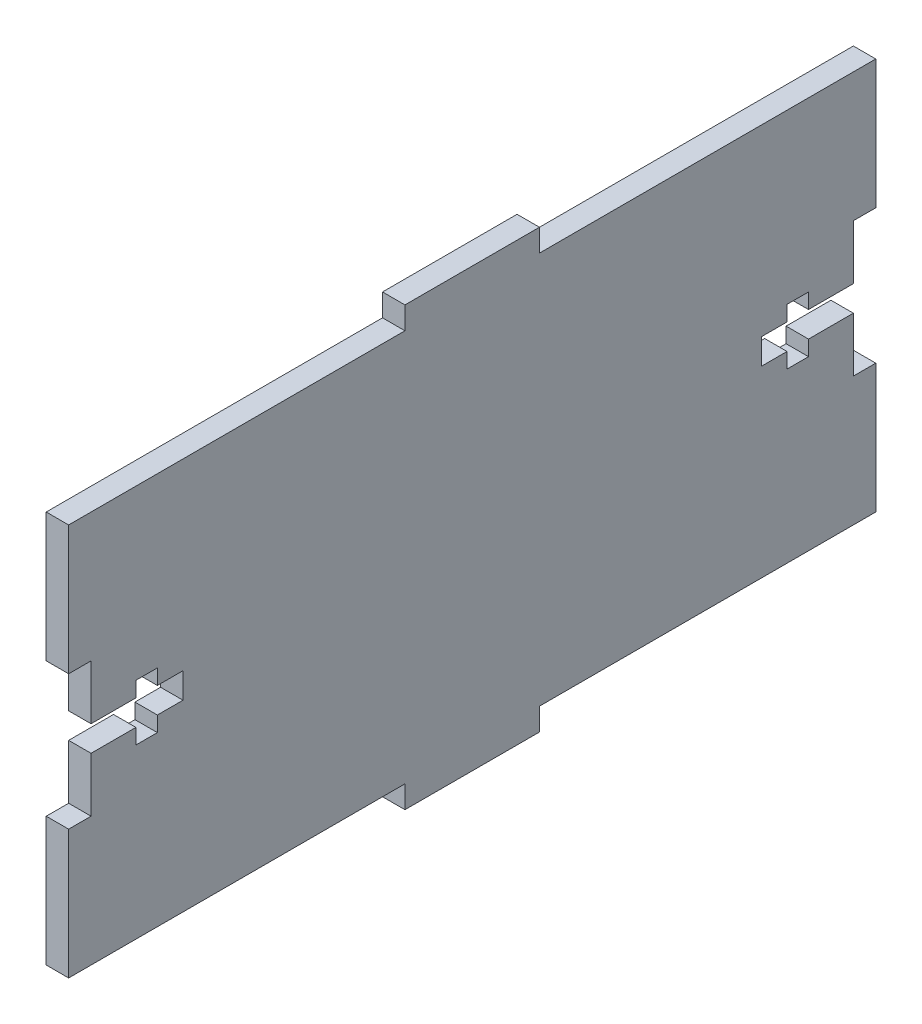
SolidWorks part; units mm, degrees
ref_plane "Front Plane" through (0, 0, 0) normal (0, 0, 1) x (1, 0, 0)
ref_plane "Top Plane" through (0, 0, 0) normal (0, 1, 0) x (1, 0, 0)
ref_plane "Right Plane" through (0, 0, 0) normal (1, 0, 0) x (0, 0, -1)
sketch "Sketch2" plane through (0, 0, 0) normal (1, 0, 0) x (0, 0, -1)
  line L0 (-45.72, 22.225) -> (-45.72, 7.62)
  line L1 (-45.72, 22.225) -> (45.72, 22.225) construction
  line L2 (-45.72, 22.225) -> (-45.72, -22.225) construction
  line L3 (-45.72, -22.225) -> (45.72, -22.225) construction
  line L4 (45.72, 22.225) -> (45.72, -22.225) construction
  line L5 (-45.72, 22.225) -> (45.72, -22.225) construction
  line L6 (-45.72, -22.225) -> (45.72, 22.225) construction
  line L7 (-45.72, 7.62) -> (-43.18, 7.62)
  line L8 (-43.18, 7.62) -> (-43.18, -7.62) construction
  line L9 (-43.18, -7.62) -> (-45.72, -7.62)
  line L10 (-45.72, -7.62) -> (-45.72, -22.225)
  line L11 (0, 22.225) -> (0, -22.225) construction
  line L12 (-45.72, 0) -> (45.72, 0) construction
  line L13 (43.18, -7.62) -> (45.72, -7.62)
  line L14 (43.18, 7.62) -> (43.18, -7.62) construction
  line L15 (45.72, 7.62) -> (43.18, 7.62)
  line L16 (-45.72, -22.225) -> (-7.62, -22.225)
  line L17 (-7.62, -22.225) -> (-7.62, -24.765)
  line L18 (-7.62, -24.765) -> (7.62, -24.765)
  line L19 (7.62, -24.765) -> (7.62, -22.225)
  line L20 (7.62, -22.225) -> (45.72, -22.225)
  line L21 (45.72, -22.225) -> (45.72, -7.62)
  line L22 (45.72, 7.62) -> (45.72, 22.225)
  line L23 (7.62, 24.765) -> (7.62, 22.225)
  line L24 (-7.62, 24.765) -> (7.62, 24.765)
  line L25 (-7.62, 22.225) -> (-7.62, 24.765)
  line L26 (45.72, 22.225) -> (7.62, 22.225)
  line L27 (-7.62, 22.225) -> (-45.72, 22.225)
  line L28 (-43.18, 7.62) -> (-43.18, 1.4478)
  line L29 (-43.18, 1.4478) -> (-38.1, 1.4478)
  line L30 (-38.1, 1.4478) -> (-38.1, 3.175)
  line L31 (-38.1, 3.175) -> (-35.6679, 3.175)
  line L32 (-35.6679, 3.175) -> (-35.6679, 1.4478)
  line L33 (-35.6679, 1.4478) -> (-32.766, 1.4478)
  line L34 (-32.766, 1.4478) -> (-32.766, -1.4478)
  line L35 (-38.1, -3.175) -> (-35.6679, -3.175)
  line L36 (-35.6679, -1.4478) -> (-32.766, -1.4478)
  line L37 (-35.6679, -3.175) -> (-35.6679, -1.4478)
  line L38 (-38.1, -1.4478) -> (-38.1, -3.175)
  line L39 (-43.18, -1.4478) -> (-38.1, -1.4478)
  line L40 (-43.18, -7.62) -> (-43.18, -1.4478)
  line L41 (43.18, -7.62) -> (43.18, -1.4478)
  line L42 (43.18, -1.4478) -> (38.1, -1.4478)
  line L43 (38.1, -1.4478) -> (38.1, -3.175)
  line L44 (38.1, -3.175) -> (35.6679, -3.175)
  line L45 (35.6679, -3.175) -> (35.6679, -1.4478)
  line L46 (35.6679, -1.4478) -> (32.766, -1.4478)
  line L47 (32.766, 1.4478) -> (32.766, -1.4478)
  line L48 (35.6679, 1.4478) -> (32.766, 1.4478)
  line L49 (35.6679, 3.175) -> (35.6679, 1.4478)
  line L50 (38.1, 3.175) -> (35.6679, 3.175)
  line L51 (38.1, 1.4478) -> (38.1, 3.175)
  line L52 (43.18, 1.4478) -> (38.1, 1.4478)
  line L53 (43.18, 7.62) -> (43.18, 1.4478)
  point P0 (0, 0)
  point P36 (-32.766, 0)
  dimension "D1" = 91.44
  dimension "D2" = 44.45
  dimension "D3" = 15.24
  dimension "D4" = 2.54
  dimension "D5" = 15.24
  dimension "D6" = 2.54
  dimension "D7" = 12.954
  dimension "D8" = 5.08
  dimension "D9" = 2.432
  dimension "D10" = 6.35
  dimension "D11" = 2.8956
extrude "Boss-Extrude1" add sketch "Sketch2" along normal blind 2.54
